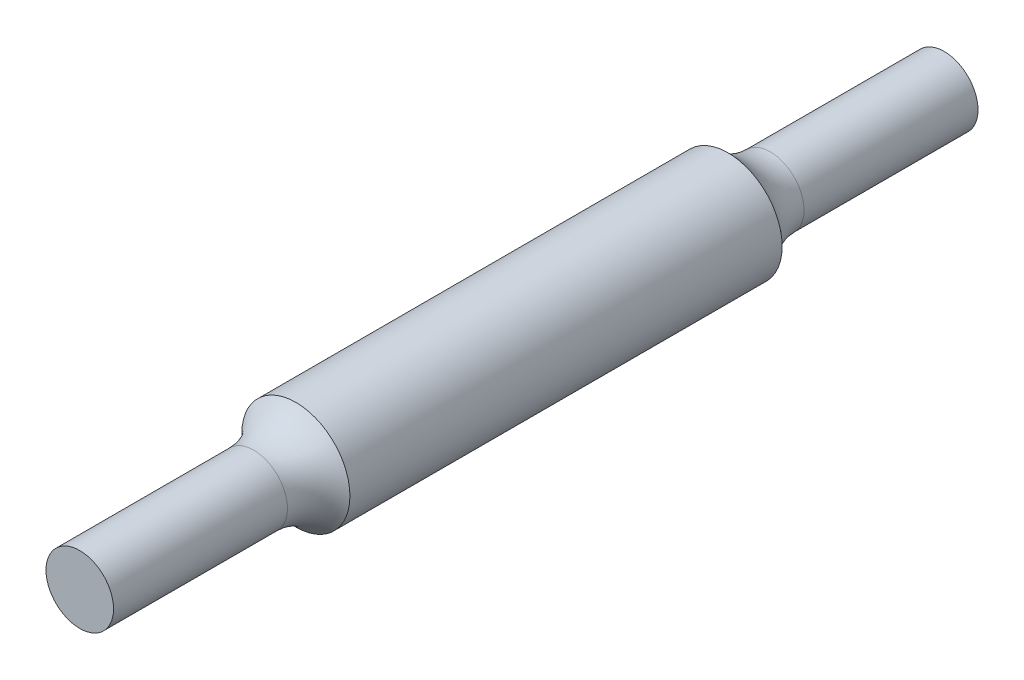
SolidWorks part; units mm, degrees
material "6061-T6 (SS)"
ref_plane "Front Plane" through (0, 0, 0) normal (0, 0, 1) x (1, 0, 0)
ref_plane "Top Plane" through (0, 0, 0) normal (0, 1, 0) x (1, 0, 0)
ref_plane "Right Plane" through (0, 0, 0) normal (1, 0, 0) x (0, 0, -1)
sketch "Sketch1" plane through (0, 0, 0) normal (0, 0, 1) x (1, 0, 0)
  circle A0 centre (0, 0) radius 6.35
  dimension "D1" = 12.7
extrude "Boss-Extrude1" add sketch "Sketch1" along normal mid plane 50.8
sketch "Sketch2" plane through (0, 0, 0) normal (0, 0, 1) x (1, 0, 0)
  circle A0 centre (0, 0) radius 3.9688
  dimension "D1" = 7.9375
extrude "Boss-Extrude2" add sketch "Sketch2" along normal mid plane 101.6
fillet "Fillet1" radius 6.35 2 edges at (3.9688, 0, -25.4) (3.9688, 0, 25.4)
sketch "Sketch3" plane through (0, 0, 0) normal (0, 1, 0) x (1, 0, 0)
  line L0 (0, 0) -> (31.5697, 0) construction
